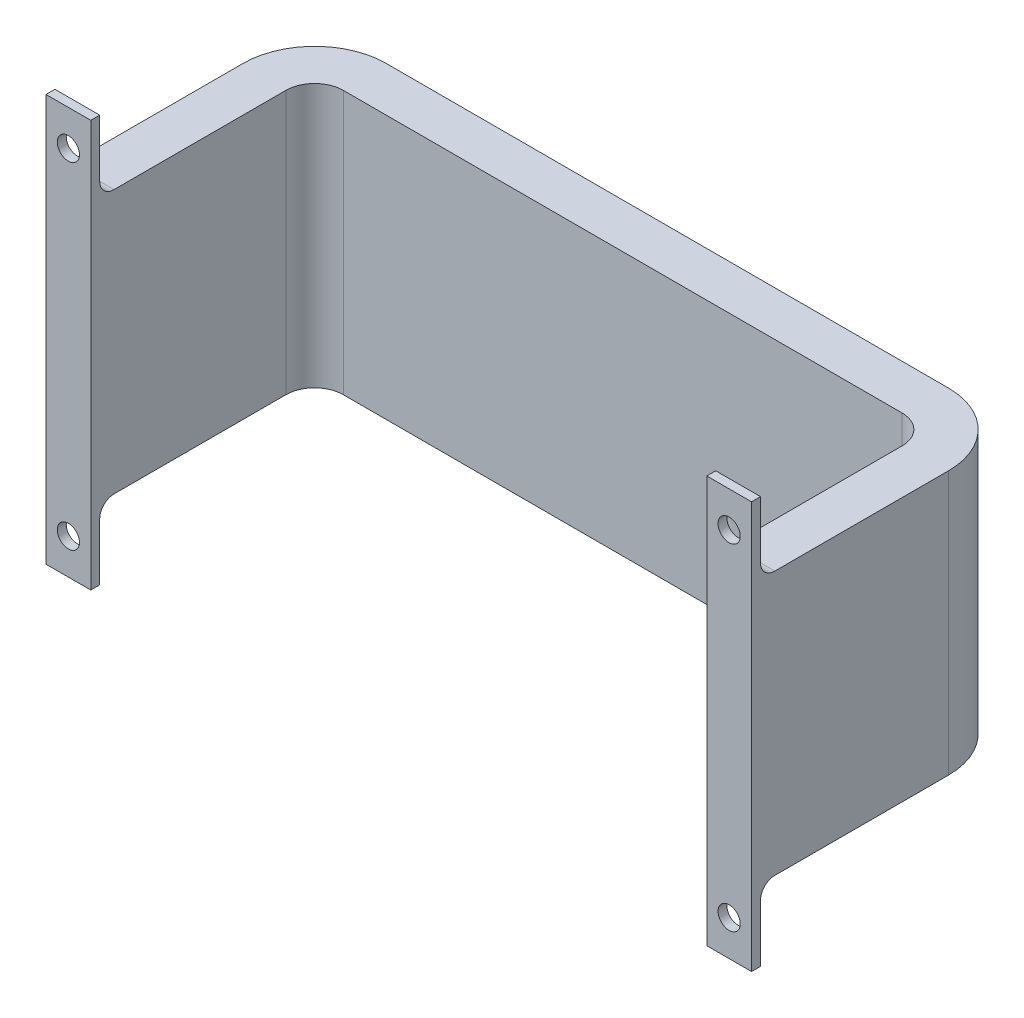
SolidWorks part; units mm, degrees
material "1060 Alloy"
ref_plane "Front Plane" through (0, 0, 0) normal (0, 0, 1) x (1, 0, 0)
ref_plane "Top Plane" through (0, 0, 0) normal (0, 1, 0) x (1, 0, 0)
ref_plane "Right Plane" through (0, 0, 0) normal (1, 0, 0) x (0, 0, -1)
sketch "Sketch1" plane through (0, 0, 0) normal (0, 0, 1) x (1, 0, 0)
  line L1 (125.095, -46.736) -> (-125.095, -46.736)
  line L2 (125.095, -46.736) -> (125.095, 46.736)
  line L3 (125.095, 46.736) -> (-125.095, 46.736)
  line L4 (-125.095, -46.736) -> (-125.095, 46.736)
  line L5 (125.095, -46.736) -> (-125.095, 46.736) construction
  line L6 (125.095, 46.736) -> (-125.095, -46.736) construction
  point P0 (0, 0)
  dimension "D1" = 93.472
  dimension "D2" = 250.19
extrude "Boss-Extrude1" add sketch "Sketch1" along normal blind 95.25
sketch "Sketch5" plane through (0, 0, 95.25) normal (0, 0, 1) x (1, 0, 0)
  line L1 (109.22, -46.736) -> (-109.22, -46.736)
  line L2 (109.22, -46.736) -> (109.22, 46.736)
  line L3 (109.22, 46.736) -> (-109.22, 46.736)
  line L4 (-109.22, -46.736) -> (-109.22, 46.736)
  line L5 (109.22, -46.736) -> (-109.22, 46.736) construction
  line L6 (109.22, 46.736) -> (-109.22, -46.736) construction
  point P0 (0, 0)
  dimension "D1" = 93.472
  dimension "D2" = 218.44
extrude "Cut-Extrude1" cut sketch "Sketch5" against normal blind 79.375
sketch "Sketch6" plane through (0, 0, 95.25) normal (0, 0, 1) x (1, 0, 0)
  line L1 (109.22, 72.136) -> (125.095, 72.136)
  line L2 (109.22, 72.136) -> (109.22, 46.736)
  line L3 (109.22, 46.736) -> (125.095, 46.736)
  line L4 (125.095, 72.136) -> (125.095, 46.736)
  line L5 (109.22, 72.136) -> (125.095, 46.736) construction
  line L6 (109.22, 46.736) -> (125.095, 72.136) construction
  line L8 (125.095, 46.736) -> (109.22, 46.736) construction
  line L9 (125.095, -46.736) -> (125.095, 46.736) construction
  line L11 (0, -51.4096) -> (0, 51.4096) construction
  line L12 (-109.22, 46.736) -> (-125.095, 46.736)
  line L13 (-125.095, 72.136) -> (-125.095, 46.736)
  line L14 (-109.22, 72.136) -> (-125.095, 72.136)
  line L15 (-109.22, 72.136) -> (-109.22, 46.736)
  line L16 (52.3875, 0) -> (-52.3875, 0) construction
  line L17 (109.22, -46.736) -> (125.095, -46.736)
  line L18 (125.095, -72.136) -> (125.095, -46.736)
  line L19 (109.22, -72.136) -> (125.095, -72.136)
  line L20 (109.22, -72.136) -> (109.22, -46.736)
  line L21 (-109.22, -72.136) -> (-109.22, -46.736)
  line L22 (-109.22, -72.136) -> (-125.095, -72.136)
  line L23 (-125.095, -72.136) -> (-125.095, -46.736)
  line L24 (-109.22, -46.736) -> (-125.095, -46.736)
  point P0 (117.1575, 59.436)
  dimension "D1" = 15.875
  dimension "D4" = 25.4
extrude "Boss-Extrude2" add sketch "Sketch6" against normal blind 3.175
sketch "Sketch7" plane through (0, 0, 92.075) normal (0, 0, -1) x (-1, 0, 0)
  line L0 (-125.095, 46.736) -> (125.095, 46.736) construction
  line L3 (117.1575, 59.5376) -> (-145.6767, 59.5376) construction
  line L6 (0, 52.3875) -> (0, -52.3875) construction
  line L7 (52.3875, 0) -> (-52.3875, 0) construction
  line L8 (0, 59.5376) -> (0, -87.3111) construction
  line L9 (-117.1575, -59.5376) -> (117.1575, -59.5376) construction
  circle A0 centre (117.1575, 59.5376) radius 3.937
  circle A1 centre (-117.1575, 59.5376) radius 3.937
  circle A2 centre (117.1575, -59.5376) radius 3.937
  circle A3 centre (-117.1575, -59.5376) radius 3.937
  dimension "D1" = 7.874
  dimension "D2" = 12.8016
  dimension "D3" = 117.1575
extrude "Cut-Extrude2" cut sketch "Sketch7" against normal through all
fillet "Fillet1" radius 25.4 1 edges at (125.095, 0, 0) type face fillet first side face at (125.095, 0, 69.85) second side face at (0, 0, 0)
fillet "Fillet2" radius 25.4 1 edges at (-125.095, 0, 0) type face fillet first side face at (-125.095, 0, 69.85) second side face at (-12.7, 0, 0)
fillet "Fillet3" radius 5.08 1 edges at (117.1575, 46.736, 92.075) type face fillet first side face at (121.0945, 59.5376, 92.075) second side face at (0, 46.736, 44.0329)
fillet "Fillet4" radius 5.08 1 edges at (-117.1575, 46.736, 92.075) type face fillet first side face at (0, 46.736, 43.0169) second side face at (-121.0945, 59.5376, 92.075)
fillet "Fillet5" radius 5.08 1 edges at (-117.1575, -46.736, 92.075) type face fillet first side face at (0, -46.736, 44.0329) second side face at (-113.2205, -59.5376, 92.075)
fillet "Fillet6" radius 5.08 1 edges at (117.1575, -46.736, 92.075) type face fillet first side face at (0, -46.736, 43.0169) second side face at (113.2205, -59.5376, 92.075)
fillet "Fillet7" radius 10.16 1 edges at (-109.22, 0, 15.875) type face fillet first side face at (-109.22, 0, 76.6644) second side face at (0, 0, 15.875)
fillet "Fillet8" radius 10.16 1 edges at (109.22, 0, 15.875) type face fillet first side face at (5.08, 0, 15.875) second side face at (109.22, 0, 76.6644)
equation "\"Height\"=3.68"
equation "\"D1@Sketch1\"=\"Height\""
equation "\"D1@Sketch5\"=\"Height\""
